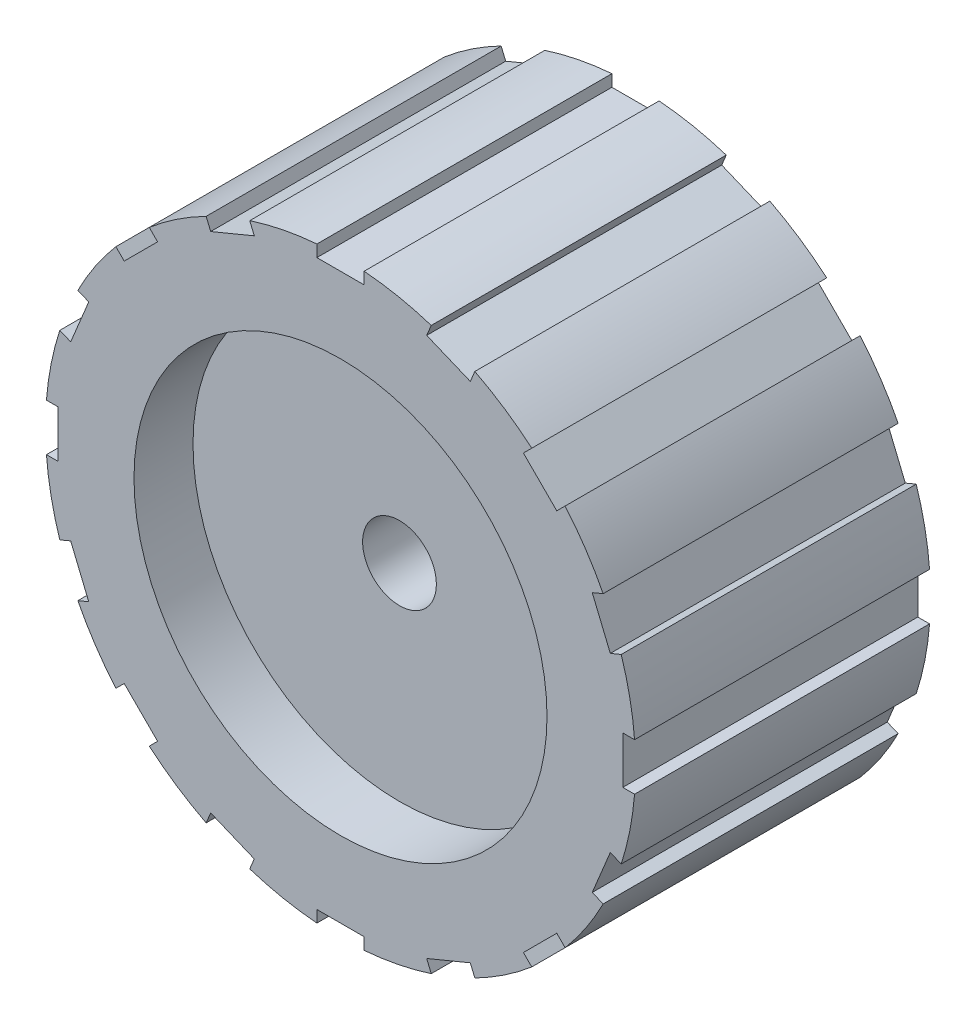
SolidWorks part; units mm, degrees
ref_plane "Front Plane" through (0, 0, 0) normal (0, 0, 1) x (1, 0, 0)
ref_plane "Top Plane" through (0, 0, 0) normal (0, 1, 0) x (1, 0, 0)
ref_plane "Right Plane" through (0, 0, 0) normal (1, 0, 0) x (0, 0, -1)
sketch "Sketch1" plane through (0, 0, 0) normal (0, 0, 1) x (1, 0, 0)
  line L0 (11.5663, 22.6137) -> (11.1775, 21.6751)
  line L2 (2.032, 25.3186) -> (2.032, 24.3026)
  line L3 (2.032, 24.3026) -> (-2.032, 24.3026)
  line L4 (-2.032, 25.3186) -> (-2.032, 24.3026)
  line L5 (11.1775, 21.6751) -> (7.4229, 23.2303)
  line L6 (7.8117, 24.1689) -> (7.4229, 23.2303)
  line L7 (19.3398, 16.4661) -> (18.6214, 15.7477)
  line L8 (18.6214, 15.7477) -> (15.7477, 18.6214)
  line L9 (16.4661, 19.3398) -> (15.7477, 18.6214)
  line L10 (24.1689, 7.8117) -> (23.2303, 7.4229)
  line L11 (23.2303, 7.4229) -> (21.6751, 11.1775)
  line L12 (22.6137, 11.5663) -> (21.6751, 11.1775)
  line L13 (25.3186, -2.032) -> (24.3026, -2.032)
  line L14 (24.3026, -2.032) -> (24.3026, 2.032)
  line L15 (25.3186, 2.032) -> (24.3026, 2.032)
  line L16 (22.6137, -11.5663) -> (21.6751, -11.1775)
  line L17 (21.6751, -11.1775) -> (23.2303, -7.4229)
  line L18 (24.1689, -7.8117) -> (23.2303, -7.4229)
  line L19 (16.4661, -19.3398) -> (15.7477, -18.6214)
  line L20 (15.7477, -18.6214) -> (18.6214, -15.7477)
  line L21 (19.3398, -16.4661) -> (18.6214, -15.7477)
  line L22 (7.8117, -24.1689) -> (7.4229, -23.2303)
  line L23 (7.4229, -23.2303) -> (11.1775, -21.6751)
  line L24 (11.5663, -22.6137) -> (11.1775, -21.6751)
  line L25 (-2.032, -25.3186) -> (-2.032, -24.3026)
  line L26 (-2.032, -24.3026) -> (2.032, -24.3026)
  line L27 (2.032, -25.3186) -> (2.032, -24.3026)
  line L28 (-11.5663, -22.6137) -> (-11.1775, -21.6751)
  line L29 (-11.1775, -21.6751) -> (-7.4229, -23.2303)
  line L30 (-7.8117, -24.1689) -> (-7.4229, -23.2303)
  line L31 (-19.3398, -16.4661) -> (-18.6214, -15.7477)
  line L32 (-18.6214, -15.7477) -> (-15.7477, -18.6214)
  line L33 (-16.4661, -19.3398) -> (-15.7477, -18.6214)
  line L34 (-24.1689, -7.8117) -> (-23.2303, -7.4229)
  line L35 (-23.2303, -7.4229) -> (-21.6751, -11.1775)
  line L36 (-22.6137, -11.5663) -> (-21.6751, -11.1775)
  line L37 (-25.3186, 2.032) -> (-24.3026, 2.032)
  line L38 (-24.3026, 2.032) -> (-24.3026, -2.032)
  line L39 (-25.3186, -2.032) -> (-24.3026, -2.032)
  line L40 (-22.6137, 11.5663) -> (-21.6751, 11.1775)
  line L41 (-21.6751, 11.1775) -> (-23.2303, 7.4229)
  line L42 (-24.1689, 7.8117) -> (-23.2303, 7.4229)
  line L43 (-16.4661, 19.3398) -> (-15.7477, 18.6214)
  line L44 (-15.7477, 18.6214) -> (-18.6214, 15.7477)
  line L45 (-19.3398, 16.4661) -> (-18.6214, 15.7477)
  line L46 (-7.8117, 24.1689) -> (-7.4229, 23.2303)
  line L47 (-7.4229, 23.2303) -> (-11.1775, 21.6751)
  line L48 (-11.5663, 22.6137) -> (-11.1775, 21.6751)
  line L49 (38.4976, 0) -> (-37.3916, 0) construction
  line L50 (0, 0) -> (0, -7.2706) construction
  arc A0 (-2.032, 25.3186) -> (-7.8117, 24.1689) centre (0, 0) ccw
  arc A1 (7.8117, 24.1689) -> (2.032, 25.3186) centre (0, 0) ccw
  arc A2 (16.4661, 19.3398) -> (11.5663, 22.6137) centre (0, 0) ccw
  arc A3 (22.6137, 11.5663) -> (19.3398, 16.4661) centre (0, 0) ccw
  arc A4 (25.3186, 2.032) -> (24.1689, 7.8117) centre (0, 0) ccw
  arc A5 (24.1689, -7.8117) -> (25.3186, -2.032) centre (0, 0) ccw
  arc A6 (19.3398, -16.4661) -> (22.6137, -11.5663) centre (0, 0) ccw
  arc A7 (11.5663, -22.6137) -> (16.4661, -19.3398) centre (0, 0) ccw
  arc A8 (2.032, -25.3186) -> (7.8117, -24.1689) centre (0, 0) ccw
  arc A9 (-7.8117, -24.1689) -> (-2.032, -25.3186) centre (0, 0) ccw
  arc A10 (-16.4661, -19.3398) -> (-11.5663, -22.6137) centre (0, 0) ccw
  arc A11 (-22.6137, -11.5663) -> (-19.3398, -16.4661) centre (0, 0) ccw
  arc A12 (-25.3186, -2.032) -> (-24.1689, -7.8117) centre (0, 0) ccw
  arc A13 (-24.1689, 7.8117) -> (-25.3186, 2.032) centre (0, 0) ccw
  arc A14 (-19.3398, 16.4661) -> (-22.6137, 11.5663) centre (0, 0) ccw
  arc A15 (-11.5663, 22.6137) -> (-16.4661, 19.3398) centre (0, 0) ccw
  circle A16 centre (0, 0) radius 17.78
  circle A17 centre (0, 0) radius 3.175
  point P7 (0, 24.3026)
  dimension "D1" = 50.8
  dimension "D5" = 35.56
  dimension "D6" = 6.35
  dimension "D3" = 1.016
  dimension "D4" = 4.064
  dimension "D2" = 16
extrude "Boss-Extrude2" add sketch "Sketch1" along normal blind 25.4 contours L48 A15 L43 L44 L45 A14 L40 L41 L42 A13 L37 L38 L39 A12 L34 L35 L36 A11 L31 L32 L33 A10 L28 L29 L30 A9 L25 L26 L27 A8 L22 L23 L24 A7 L19 L20 L21 A6 L16 L17 L18 A5 L13 L14 L15 A4 L10 L11 L12 A3 L7 region at (13.7136, 20.5239, 0)
extrude "Boss-Extrude3" add sketch "Sketch1<3>" along direction (0, 0, 1) on the side of the normal blind 20.32 contours A16 A17 region at (-17.2771, 0, 0)
sketch "Sketch1<3>" plane through (0, 0, 0) normal (0, 0, 1) x (1, 0, 0) same geometry as "Sketch1"
extrude "Cut-Extrude1" cut sketch "Sketch1<4>" along normal blind 5.08 contours A16 A17 region at (-17.2771, 0, 0)
sketch "Sketch1<4>" plane through (0, 0, 0) normal (0, 0, 1) x (1, 0, 0) same geometry as "Sketch1"
